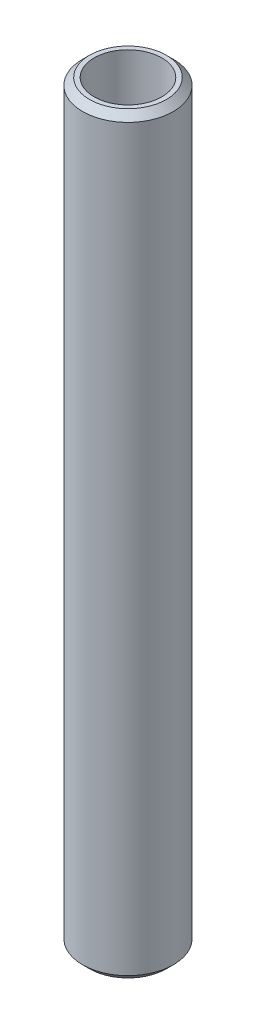
SolidWorks part; units mm, degrees
ref_plane "Front Plane" through (0, 0, 0) normal (0, 0, 1) x (1, 0, 0)
ref_plane "Top Plane" through (0, 0, 0) normal (0, 1, 0) x (1, 0, 0)
ref_plane "Right Plane" through (0, 0, 0) normal (1, 0, 0) x (0, 0, -1)
sketch "Sketch1" plane through (0, 0, 0) normal (0, 1, 0) x (1, 0, 0)
  circle A0 centre (0, 0) radius 22.5
  dimension "SHAFT_OD" = 45
extrude "Boss-Extrude1" add sketch "Sketch1" along normal blind 373.4909
sketch "Sketch2" plane through (0, 0, 0) normal (0, 1, 0) x (1, 0, 0)
  circle A0 centre (0, 0) radius 16.7844
  dimension "BORE_D" = 33.5687
extrude "Cut-Extrude1" cut sketch "Sketch2" along normal through all
chamfer "Chamfer1" distance 3.4448 angle 45 2 edges at (0, 373.4909, 22.5) (0, 0, 22.5)
